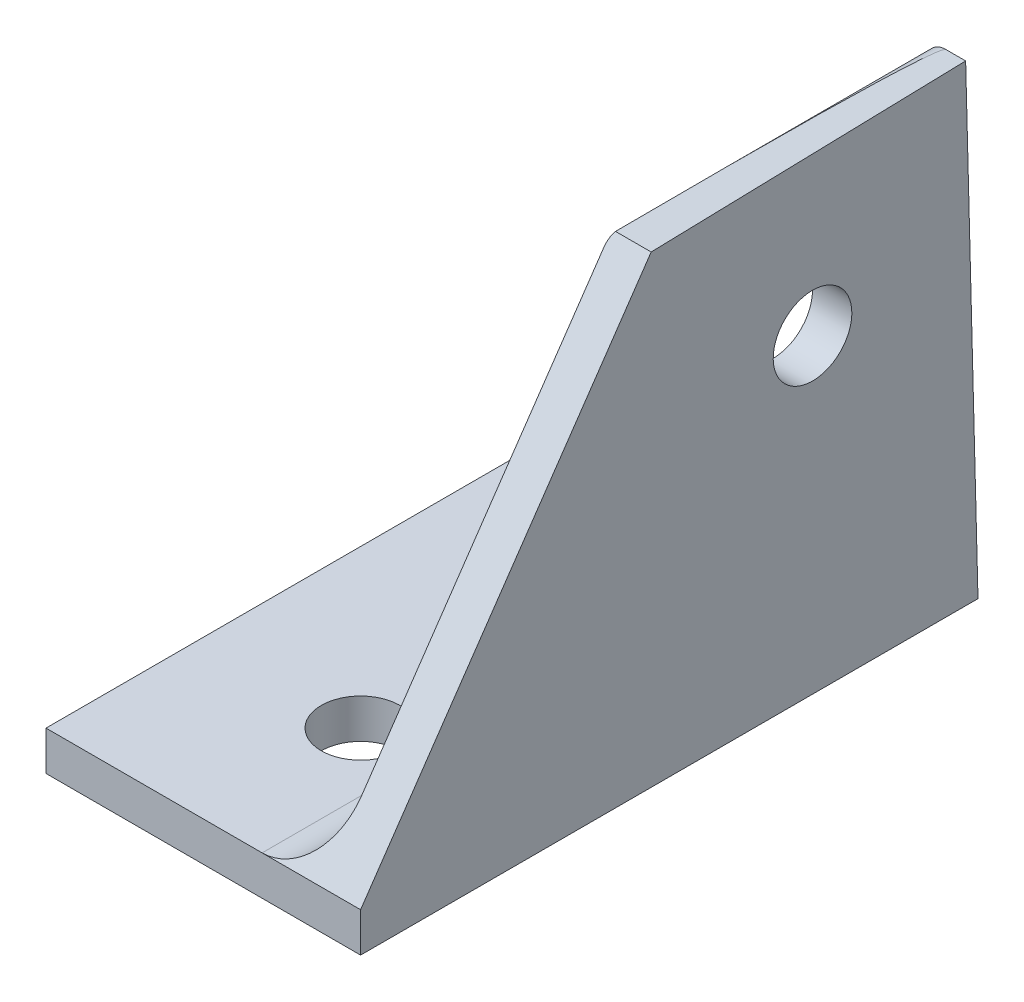
SolidWorks part; units mm, degrees
ref_plane "Front Plane" through (0, 0, 0) normal (0, 0, 1) x (1, 0, 0)
ref_plane "Top Plane" through (0, 0, 0) normal (0, 1, 0) x (1, 0, 0)
ref_plane "Right Plane" through (0, 0, 0) normal (1, 0, 0) x (0, 0, -1)
sketch "Sketch0" plane through (0, 0, 0) normal (0, 0, 1) x (1, 0, 0)
  line L0 (-19.05, -19.05) -> (19.05, -19.05)
  line L1 (19.05, -19.05) -> (19.05, 19.05)
  line L2 (19.05, 0) -> (0, 0) construction
  line L3 (0, 0) -> (0, -19.05) construction
  line L4 (15.875, -11.0998) -> (15.875, 19.05) construction
  line L5 (11.0998, -15.875) -> (-19.05, -15.875) construction
  arc A0 (15.875, -11.0998) -> (11.0998, -15.875) centre (11.0998, -11.0998) cw
  point P3 (14.4764, -14.4764)
  dimension "Inside Corner Radius" = 4.7752
  dimension "Outside Height" = 38.1
  dimension "Inside Height" = 34.925
  dimension "Inside Width" = 34.925
  dimension "Wall Thickness" = 3.175
  dimension "D1" = 3.175
  dimension "Outside Width" = 38.1
sketch "Sketch1" plane through (0, 0, 0) normal (1, 0, 0) x (0, 0, -1)
  line L0 (25.4, 0) -> (-25.4, 0)
  point P4 (0, 0)
  dimension "Length" = 50.8
sketch "Sketch2" plane through (0, 0, 0) normal (0, 0, 1) x (1, 0, 0)
  line L0 (-19.05, -19.05) -> (19.05, -19.05)
  line L1 (19.05, -19.05) -> (19.05, 19.05)
  line L2 (19.05, 19.05) -> (15.875, 19.05) construction
  line L3 (15.875, 17.4625) -> (15.875, -11.0998)
  line L4 (11.0998, -15.875) -> (-17.4625, -15.875)
  line L5 (-19.05, -19.05) -> (-19.05, -15.875) construction
  line L6 (17.4625, 19.05) -> (19.05, 19.05)
  line L7 (-19.05, -17.4625) -> (-19.05, -19.05)
  line L8 (19.05, 0) -> (0, 0) construction
  line L9 (0, 0) -> (0, -19.05) construction
  arc A0 (15.875, 17.4625) -> (17.4625, 19.05) centre (17.4625, 17.4625) cw
  arc A1 (-19.05, -17.4625) -> (-17.4625, -15.875) centre (-17.4625, -17.4625) cw
  arc A2 (15.875, -11.0998) -> (11.0998, -15.875) centre (11.0998, -11.0998) cw
  dimension "Inside Radius" = 4.7752
  dimension "Height" = 38.1
  dimension "Width" = 38.1
  dimension "Thickness" = 3.175
extrude "Boss-Extrude1" add sketch "Sketch2" along normal mid plane 50.8
sketch "Break Locations" plane through (0, 0, 0) normal (1, 0, 0) x (0, 0, -1)
  line L0 (13.462, 0) -> (-13.462, 0)
  line L1 (-25.4, -19.05) -> (-25.4, 19.05) construction
  line L2 (25.4, -19.05) -> (25.4, 19.05) construction
  point P0 (6.985, 0)
  point P1 (-6.985, 0)
  point P10 (0, 0)
  point P11 (-13.462, 0)
  point P13 (13.462, 0)
  dimension "D1" = 32.385
  dimension "D2" = 32.385
  dimension "D3" = 38.862
sketch "Sketch3" plane through (0, -19.05, 0) normal (0, -1, 0) x (1, 0, 0)
  line L0 (19.05, 25.4) -> (6.35, 25.4) construction
  line L1 (-19.05, 25.4) -> (19.05, 25.4) construction
  line L2 (6.35, 25.4) -> (6.35, 12.7) construction
  line L3 (6.35, 12.7) -> (6.35, -12.7) construction
  line L4 (-19.05, 25.4) -> (-6.35, 25.4)
  line L5 (-6.35, 25.4) -> (-6.35, -25.4)
  line L6 (-19.05, -25.4) -> (19.05, -25.4) construction
  line L7 (-6.35, -25.4) -> (-19.05, -25.4)
  line L8 (-19.05, -25.4) -> (-19.05, 25.4)
  circle A0 centre (6.35, 12.7) radius 3.175
  circle A1 centre (6.35, -12.7) radius 3.175
  dimension "D4" = 12.7
  dimension "D1" = 12.7
  dimension "D2" = 12.7
  dimension "D3" = 25.4
extrude "Cut-Extrude1" cut sketch "Sketch3" against normal through all
sketch "Sketch12" plane through (19.05, 0, 0) normal (1, 0, 0) x (0, 0, -1)
  line L0 (23.4518, 19.05) -> (24.4495, -19.05)
  line L1 (24.3992, -17.1295) -> (10.8021, 502.1225) construction
  line L2 (-25.4, 19.05) -> (25.4, 19.05) construction
  line L3 (-25.4, -19.05) -> (25.4, -19.05) construction
  line L4 (23.4518, 19.05) -> (-1.9395, 18.3851)
  line L5 (-1.9395, 18.3851) -> (-25.4, -15.875)
  line L6 (-25.4, -19.05) -> (-25.4, 19.05) construction
  line L7 (-25.4, -15.875) -> (-25.4, -19.05)
  line L8 (-25.4, -19.05) -> (24.4495, -19.05)
  dimension "D1" = 3.175
extrude "Cut-Extrude2" cut sketch "Sketch12" against normal through all flip side to cut
sketch "Sketch13" plane through (19.05, 0, 0) normal (1, 0, 0) x (0, 0, -1)
  line L0 (10.7562, 18.7176) -> (11.0886, 6.0219) construction
  line L1 (23.4518, 19.05) -> (-1.9395, 18.3851) construction
  circle A0 centre (11.0886, 6.0219) radius 3.175
extrude "Cut-Extrude3" cut sketch "Sketch13" against normal through all
equation "\"D1@Break Locations\" = .85 * \"Height@Sketch2\""
equation "\"D2@Break Locations\"=\"D1@Break Locations\""
equation "\"Thickness@Sketch2\"=\"wall thickness@sketch0\""
equation "\"Height@Sketch2\"=\"outside height@sketch0\""
equation "\"Width@Sketch2\"=\"outside width@sketch0\""
equation "\"Inside Radius@Sketch2\"=\"inside corner radius@sketch0\""
equation "\"Length@Boss-Extrude1\"=\"length@sketch1\""
equation "\"D3@Break Locations\"=\"D2@Break Locations\"*1.2"
equation "\"D1@Sketch0\"=\"Wall Thickness@Sketch0\""
